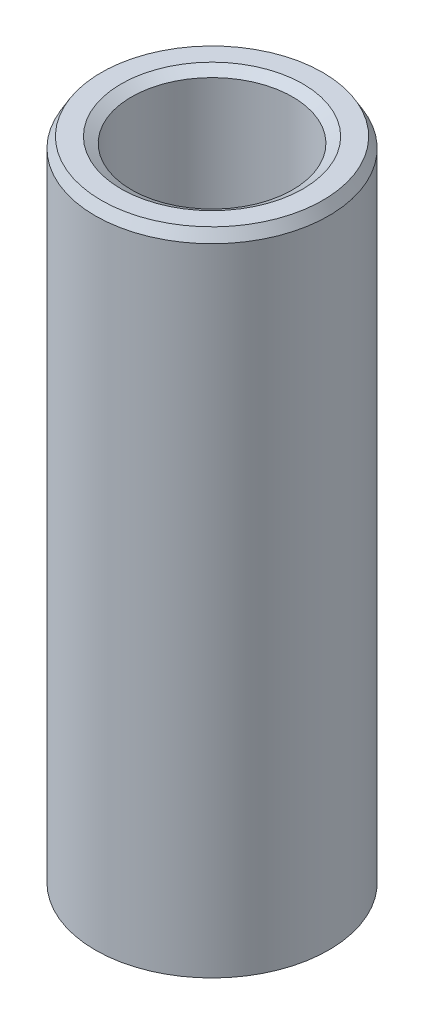
SolidWorks part; units mm, degrees
ref_plane "Front Plane" through (0, 0, 0) normal (0, 0, 1) x (1, 0, 0)
ref_plane "Top Plane" through (0, 0, 0) normal (0, 1, 0) x (1, 0, 0)
ref_plane "Right Plane" through (0, 0, 0) normal (1, 0, 0) x (0, 0, -1)
sketch "Sketch1" plane through (0, 0, 0) normal (0, 1, 0) x (1, 0, 0)
  circle A0 centre (0, 0) radius 40
  dimension "SLEEVE_OD" = 80
extrude "Boss-Extrude1" add sketch "Sketch1" along normal blind 223.4452
sketch "Sketch2" plane through (0, 0, 0) normal (0, 1, 0) x (1, 0, 0)
  circle A0 centre (0, 0) radius 27.5955
  dimension "BORE_D" = 55.191
extrude "Cut-Extrude1" cut sketch "Sketch2" along normal through all
chamfer "Chamfer1" distance 3.5623 angle 30 4 edges at (0, 223.4452, 27.5955) (0, 0, 27.5955) (0, 0, 40) (0, 223.4452, 40) first distance on face at (0, 223.4452, 27.5955) first distance on face at (0, 0, 27.5955) first distance on face at (0, 223.4452, 40)
